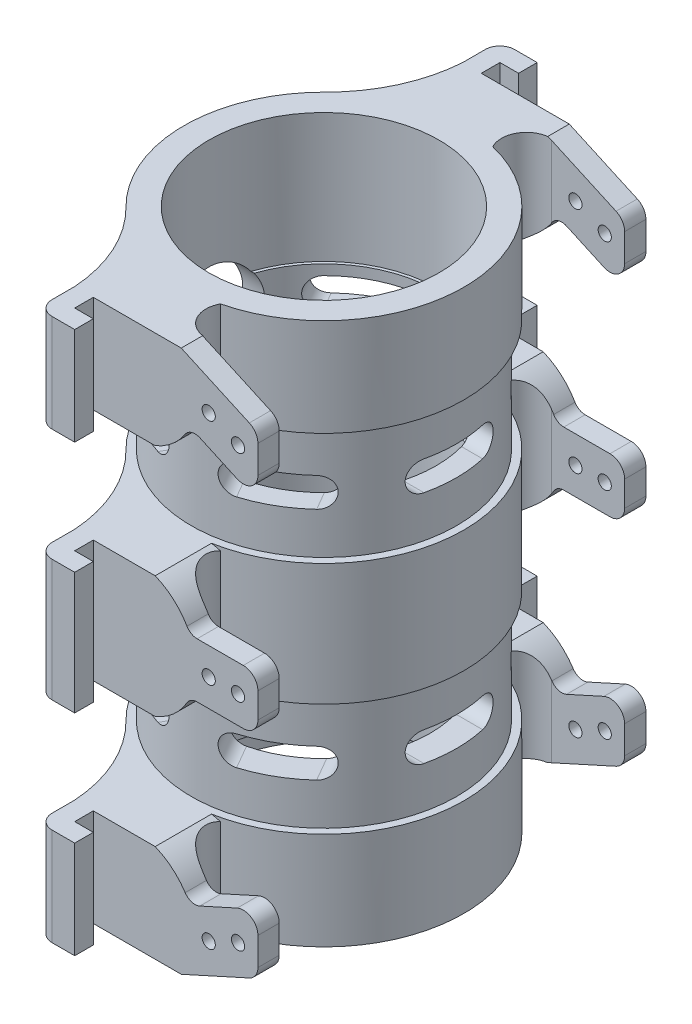
SolidWorks part; units mm, degrees
ref_plane "Front Plane" through (0, 0, 0) normal (0, 0, 1) x (1, 0, 0)
ref_plane "Top Plane" through (0, 0, 0) normal (0, 1, 0) x (1, 0, 0)
ref_plane "Right Plane" through (0, 0, 0) normal (1, 0, 0) x (0, 0, -1)
sketch "Sketch1" plane through (0, 0, 0) normal (0, 1, 0) x (1, 0, 0)
  line L0 (0, 38.25) -> (0, 45.25) construction
  circle A0 centre (0, 0) radius 38.25
  circle A1 centre (0, 0) radius 45.25
  dimension "D1" = 76.5
  dimension "D2" = 7
extrude "Boss-Extrude1" add sketch "Sketch1" along normal mid plane 185
sketch "Sketch2" plane through (0, -92.5, 0) normal (0, -1, 0) x (1, 0, 0)
  line L0 (0, 36.25) -> (0, 38.25) construction
  circle A0 centre (0, 0) radius 36.25
  circle A1 centre (0, 0) radius 38.25 construction
  circle A2 centre (0, 0) radius 38.25
  dimension "D1" = 2
extrude "Boss-Extrude2" add sketch "Sketch2" against normal blind 100 from offset 6.35 offset against normal yes
sketch "Sketch6" plane through (0, 92.5, 0) normal (0, 1, 0) x (1, 0, 0)
  line L0 (0, 38.25) -> (0, 39.25) construction
  circle A0 centre (0, 0) radius 39.25
  circle A1 centre (0, 0) radius 38.25 construction
  circle A2 centre (0, 0) radius 38.25
  dimension "D1" = 1
extrude "Cut-Extrude3" cut sketch "Sketch6" against normal blind 44
sketch "Sketch7" plane through (0, 0, 0) normal (1, 0, 0) x (0, 0, -1)
  line L0 (45.25, 92.5) -> (-45.25, 92.5) construction
  circle A0 centre (0, 40) radius 15
  dimension "D2" = 30
  dimension "D1" = 52.5
extrude "Cut-Extrude4" cut sketch "Sketch7" against normal through all
sketch "Sketch8" plane through (0, 0, 0) normal (0, 1, 0) x (1, 0, 0)
  line L1 (17.5, -66.175) -> (128.1882, -66.175) construction
  line L2 (-18.85, -66.175) -> (-18.85, -78.875)
  line L3 (-18.85, -78.875) -> (-6.15, -78.875)
  line L4 (45.25, 0) -> (-45.25, 0) construction
  line L5 (31.75, 0) -> (50, 0) construction
  line L6 (-6.15, -78.875) -> (-6.15, -72.525)
  line L7 (-12.5, -72.525) -> (17.5, -72.525) construction
  line L8 (-6.15, -72.525) -> (-12.5, -72.525)
  line L9 (-12.5, -72.525) -> (-12.5, -66.175)
  line L10 (-12.5, -66.175) -> (43.65, -66.175)
  line L11 (-12.5, 66.175) -> (43.65, 66.175)
  line L12 (-12.5, 72.525) -> (-12.5, 66.175)
  line L13 (-6.15, 72.525) -> (-12.5, 72.525)
  line L14 (-6.15, 78.875) -> (-6.15, 72.525)
  line L15 (-18.85, 78.875) -> (-6.15, 78.875)
  line L16 (-18.85, 66.175) -> (-18.85, 78.875)
  line L18 (43.65, -66.175) -> (43.65, -58.9107)
  line L19 (43.65, -58.9107) -> (18.65, -58.9107)
  line L20 (43.65, 58.9107) -> (18.65, 58.9107)
  line L21 (43.65, 66.175) -> (43.65, 58.9107)
  line L22 (-12.5, -72.525) -> (-18.85, -72.525) construction
  arc A0 (-32.8241, -31.1471) -> (-18.85, -66.175) centre (-69.7381, -66.175) cw
  circle A1 centre (0, 0) radius 45.25 construction
  arc A2 (-32.8241, -31.1471) -> (15.7007, -42.4388) centre (0, 0) ccw
  arc A3 (-32.8241, 31.1471) -> (15.7007, 42.4388) centre (0, 0) cw
  arc A4 (-32.8241, 31.1471) -> (-18.85, 66.175) centre (-69.7381, 66.175) ccw
  arc A9 (18.65, -58.9107) -> (15.7007, -42.4388) centre (18.65, -50.4107) cw
  arc A10 (18.65, 58.9107) -> (15.7007, 42.4388) centre (18.65, 50.4107) ccw
  point P6 (-18.6446, -78.6696)
  point P41 (0, 0)
  dimension "D1" = 8.5
  dimension "D2" = 62.5
  dimension "D3" = 25
extrude "Boss-Extrude3" add sketch "Sketch8" along normal up to surface and the other way up to surface up to face at (0, 92.5, 39.25) other way up to face at (0, -92.5, 45.25)
sketch "Sketch10" plane through (0, 0, 66.175) normal (0, 0, 1) x (1, 0, 0)
  line L0 (17.5, -92.5) -> (43.65, -92.5)
  line L1 (43.65, -92.5) -> (43.65, -80.6536)
  line L2 (-6.15, -59.2129) -> (-32.8241, -59.2129)
  line L3 (128.1882, -42.3564) -> (17.5, -92.5) construction
  line L4 (43.65, -80.6536) -> (17.5, -92.5)
  line L5 (43.65, 80.6536) -> (43.65, 92.5)
  line L6 (17.5, 92.5) -> (128.1882, 42.3564) construction
  line L7 (43.65, 92.5) -> (17.5, 92.5)
  line L8 (-12.5, 92.5) -> (43.65, 92.5) construction
  line L9 (17.5, 92.5) -> (43.65, 80.6536)
  line L10 (43.65, -60.1882) -> (43.65, -9.3209)
  line L11 (79.953, -43.7423) -> (23.8431, -69.161) construction
  line L12 (22.9086, -9.3209) -> (60.2886, -9.3209) construction
  line L21 (22.9086, -9.3209) -> (43.65, -9.3209)
  line L23 (43.65, -60.1882) -> (23.8431, -69.161)
  line L25 (-6.15, 92.5) -> (-6.15, -92.5) construction
  line L26 (-32.8241, 92.5) -> (-32.8241, -92.5) construction
  line L32 (-32.8241, -59.2129) -> (-32.8241, -20.7871)
  line L36 (-32.8241, -20.7871) -> (-6.15, -20.7871)
  line L40 (0, 0) -> (-32.8241, 0) construction
  line L45 (8.611, -59.2129) -> (-6.15, -59.2129)
  line L46 (8.611, -20.7871) -> (-6.15, -20.7871)
  line L47 (-32.8241, 59.2129) -> (-32.8241, 20.7871)
  line L48 (-6.15, 59.2129) -> (-32.8241, 59.2129)
  line L49 (8.611, 59.2129) -> (-6.15, 59.2129)
  line L50 (43.65, 60.1882) -> (23.8431, 69.161)
  line L51 (43.65, 60.1882) -> (43.65, 9.3209)
  line L52 (22.9086, 9.3209) -> (43.65, 9.3209)
  line L53 (8.611, 20.7871) -> (-6.15, 20.7871)
  line L54 (-32.8241, 20.7871) -> (-6.15, 20.7871)
  line L55 (43.65, 92.5) -> (43.65, -92.5) construction
  arc A6 (18.8427, -67.7035) -> (23.8431, -69.161) centre (22.1925, -65.5175) ccw construction
  arc A7 (18.8427, -67.7035) -> (8.611, -59.2129) centre (0, -80) ccw construction
  arc A10 (8.611, -20.7871) -> (19.4507, -11.3102) centre (0, 0) ccw construction
  arc A11 (22.9086, -9.3209) -> (19.4507, -11.3102) centre (22.9086, -13.3209) ccw construction
  arc A18 (18.8427, -67.7035) -> (23.8431, -69.161) centre (22.1925, -65.5175) ccw
  arc A19 (18.8427, -67.7035) -> (8.611, -59.2129) centre (0, -80) ccw
  arc A22 (8.611, -20.7871) -> (19.4507, -11.3102) centre (0, 0) ccw
  arc A23 (22.9086, -9.3209) -> (19.4507, -11.3102) centre (22.9086, -13.3209) ccw
  arc A24 (18.8427, 67.7035) -> (8.611, 59.2129) centre (0, 80) cw
  arc A25 (18.8427, 67.7035) -> (23.8431, 69.161) centre (22.1925, 65.5175) cw
  arc A26 (22.9086, 9.3209) -> (19.4507, 11.3102) centre (22.9086, 13.3209) cw
  arc A27 (8.611, 20.7871) -> (19.4507, 11.3102) centre (0, 0) cw
extrude "Cut-Extrude6" cut sketch "Sketch10" against normal up to surface and the other way through all up to face at (-45.1776, 54.7802, 2.5586)
sketch "Sketch11" plane through (0, 0, -78.875) normal (0, 0, -1) x (-1, 0, 0)
  line L3 (-43.65, 92.5) -> (-43.65, 80.6536)
  line L4 (-17.5, 92.5) -> (-43.65, 92.5)
  line L5 (-43.65, 80.6536) -> (-17.5, 92.5)
  line L6 (-43.65, 92.5) -> (-43.65, 80.6536)
  line L7 (-17.5, 92.5) -> (-43.65, 92.5)
  line L8 (-43.65, 80.6536) -> (-17.5, 92.5)
  line L9 (-43.65, -92.5) -> (-17.5, -92.5)
  line L10 (-43.65, -80.6536) -> (-43.65, -92.5)
  line L11 (-17.5, -92.5) -> (-43.65, -80.6536)
  line L12 (-43.65, -92.5) -> (-17.5, -92.5)
  line L13 (-43.65, -80.6536) -> (-43.65, -92.5)
  line L14 (-17.5, -92.5) -> (-43.65, -80.6536)
  line L20 (32.8241, 20.7871) -> (32.8241, 59.2129)
  line L21 (6.15, 20.7871) -> (32.8241, 20.7871)
  line L22 (-8.611, 20.7871) -> (6.15, 20.7871)
  line L23 (-43.65, 9.3209) -> (-22.9086, 9.3209)
  line L24 (-43.65, 60.1882) -> (-43.65, 9.3209)
  line L25 (-23.8431, 69.161) -> (-43.65, 60.1882)
  line L26 (6.15, 59.2129) -> (-8.611, 59.2129)
  line L27 (32.8241, 59.2129) -> (6.15, 59.2129)
  line L28 (32.8241, 20.7871) -> (32.8241, 59.2129)
  line L29 (6.15, 20.7871) -> (32.8241, 20.7871)
  line L30 (-8.611, 20.7871) -> (6.15, 20.7871)
  line L31 (-43.65, 9.3209) -> (-22.9086, 9.3209)
  line L32 (-43.65, 60.1882) -> (-43.65, 9.3209)
  line L33 (-23.8431, 69.161) -> (-43.65, 60.1882)
  line L34 (6.15, 59.2129) -> (-8.611, 59.2129)
  line L35 (32.8241, 59.2129) -> (6.15, 59.2129)
  line L36 (-22.9086, -9.3209) -> (-43.65, -9.3209)
  line L37 (-43.65, -9.3209) -> (-43.65, -60.1882)
  line L38 (-43.65, -60.1882) -> (-23.8431, -69.161)
  line L39 (-8.611, -59.2129) -> (6.15, -59.2129)
  line L40 (6.15, -59.2129) -> (32.8241, -59.2129)
  line L41 (32.8241, -59.2129) -> (32.8241, -20.7871)
  line L42 (32.8241, -20.7871) -> (6.15, -20.7871)
  line L43 (6.15, -20.7871) -> (-8.611, -20.7871)
  line L44 (-22.9086, -9.3209) -> (-43.65, -9.3209)
  line L45 (-43.65, -9.3209) -> (-43.65, -60.1882)
  line L46 (-43.65, -60.1882) -> (-23.8431, -69.161)
  line L47 (-8.611, -59.2129) -> (6.15, -59.2129)
  line L48 (6.15, -59.2129) -> (32.8241, -59.2129)
  line L49 (32.8241, -59.2129) -> (32.8241, -20.7871)
  line L50 (32.8241, -20.7871) -> (6.15, -20.7871)
  line L51 (6.15, -20.7871) -> (-8.611, -20.7871)
  arc A4 (-8.611, 20.7871) -> (-19.4507, 11.3102) centre (0, 0) ccw
  arc A5 (-22.9086, 9.3209) -> (-19.4507, 11.3102) centre (-22.9086, 13.3209) ccw
  arc A6 (-18.8427, 67.7035) -> (-23.8431, 69.161) centre (-22.1925, 65.5175) ccw
  arc A7 (-18.8427, 67.7035) -> (-8.611, 59.2129) centre (0, 80) ccw
  arc A8 (-8.611, 20.7871) -> (-19.4507, 11.3102) centre (0, 0) ccw
  arc A9 (-22.9086, 9.3209) -> (-19.4507, 11.3102) centre (-22.9086, 13.3209) ccw
  arc A10 (-18.8427, 67.7035) -> (-23.8431, 69.161) centre (-22.1925, 65.5175) ccw
  arc A11 (-18.8427, 67.7035) -> (-8.611, 59.2129) centre (0, 80) ccw
  arc A12 (-23.8431, -69.161) -> (-18.8427, -67.7035) centre (-22.1925, -65.5175) ccw
  arc A13 (-8.611, -59.2129) -> (-18.8427, -67.7035) centre (0, -80) ccw
  arc A14 (-19.4507, -11.3102) -> (-8.611, -20.7871) centre (0, 0) ccw
  arc A15 (-19.4507, -11.3102) -> (-22.9086, -9.3209) centre (-22.9086, -13.3209) ccw
  arc A16 (-23.8431, -69.161) -> (-18.8427, -67.7035) centre (-22.1925, -65.5175) ccw
  arc A17 (-8.611, -59.2129) -> (-18.8427, -67.7035) centre (0, -80) ccw
  arc A18 (-19.4507, -11.3102) -> (-8.611, -20.7871) centre (0, 0) ccw
  arc A19 (-19.4507, -11.3102) -> (-22.9086, -9.3209) centre (-22.9086, -13.3209) ccw
  dimension "D1" = 0
  dimension "D2" = 0
  dimension "D3" = 0
  dimension "D4" = 0
extrude "Cut-Extrude7" cut sketch "Sketch11" against normal up to surface (66.9486 mm away) up to face at (-3.9052, 0.3336, 17.6166)
fillet "Fillet4" radius 5 12 edges at (43.65, 80.6536, -62.5429) (43.65, 60.1882, -62.5429) (43.65, 9.3209, -62.5429) (43.65, -9.3209, -62.5429) (43.65, -60.1882, -62.5429) (43.65, -80.6536, -62.5429) (43.65, -80.6536, 62.5429) (43.65, -60.1882, 62.5429) (43.65, -9.3209, 62.5429) (43.65, 9.3209, 62.5429) (43.65, 60.1882, 62.5429) (43.65, 80.6536, 62.5429)
fillet "Fillet5" radius 5 6 edges at (-18.85, -75.8565, -78.875) (-18.85, 0, -78.875) (-18.85, 75.8565, -78.875) (-18.85, 0, 78.875) (-18.85, -75.8565, 78.875) (-18.85, 75.8565, 78.875)
sketch "Sketch14" plane through (0, 0, -66.175) normal (0, 0, -1) x (-1, 0, 0)
  line L0 (-36.867, 73.4937) -> (-26.867, 78.0239) construction
  line L1 (-17.5, 92.5) -> (-40.7132, 81.984) construction
  line L2 (-40.7132, 81.984) -> (-33.0207, 65.0034) construction
  line L3 (-36.5868, 63.3879) -> (-23.8431, 69.161) construction
  line L4 (0, 0) -> (-36.867, 0) construction
  line L5 (-26.867, 78.0239) -> (-26.867, 0) construction
  circle A2 centre (-36.867, 73.4937) radius 2.25
  circle A3 centre (-26.867, 78.0239) radius 2.25
  circle A4 centre (-36.867, 0) radius 2.25
  circle A5 centre (-26.867, 0) radius 2.25
  circle A6 centre (-36.867, -73.4937) radius 2.25
  circle A7 centre (-26.867, -78.0239) radius 2.25
  point P16 (-36.867, 73.4937)
  dimension "D1" = 4.5
  dimension "D2" = 10
extrude "Cut-Extrude8" cut sketch "Sketch14" against normal up to surface (7.2643 mm away) up to face at (30.7785, -73.3041, -58.9107)
sketch "Sketch15" plane through (0, 0, 66.175) normal (0, 0, 1) x (1, 0, 0)
  circle A1 centre (36.867, -73.4937) radius 2.25
  circle A2 centre (36.867, -73.4937) radius 2.25
  circle A3 centre (36.867, 0) radius 2.25
  circle A4 centre (36.867, 0) radius 2.25
  circle A5 centre (26.867, 78.0239) radius 2.25
  circle A6 centre (26.867, 78.0239) radius 2.25
  circle A7 centre (36.867, 73.4937) radius 2.25
  circle A8 centre (36.867, 73.4937) radius 2.25
  circle A9 centre (26.867, -78.0239) radius 2.25
  circle A10 centre (26.867, -78.0239) radius 2.25
  circle A11 centre (26.867, 0) radius 2.25
  circle A12 centre (26.867, 0) radius 2.25
  dimension "D1" = 0
  dimension "D2" = 0
  dimension "D3" = 0
  dimension "D4" = 0
  dimension "D5" = 0
  dimension "D6" = 0
extrude "Cut-Extrude9" cut sketch "Sketch15" against normal up to surface (7.2643 mm away) up to face at (30.7785, -73.3041, 58.9107)
sketch "Sketch16" plane through (0, 92.5, 0) normal (0, 1, 0) x (1, 0, 0)
  line L0 (-45.25, 0) -> (-47.75, 0) construction
  circle A0 centre (0, 0) radius 47.75
  circle A1 centre (0, 0) radius 45.25
  arc A2 (-32.8241, 31.1471) -> (-32.8241, -31.1471) centre (0, 0) ccw construction
  dimension "D1" = 2.5
extrude "Boss-Extrude4" add sketch "Sketch16" against normal up to surface (33.2871 mm away) up to face at (-10.3824, 59.2129, 65.577)
sketch "Sketch17" plane through (0, -92.5, 0) normal (0, -1, 0) x (1, 0, 0)
  circle A1 centre (0, 0) radius 45.25
  circle A2 centre (0, 0) radius 45.25
  circle A3 centre (0, 0) radius 47.75
  circle A4 centre (0, 0) radius 47.75
  dimension "D1" = 0
  dimension "D2" = 0
extrude "Boss-Extrude5" add sketch "Sketch17" against normal up to surface (33.2871 mm away) up to face at (-10.3824, -59.2129, 65.577)
sketch "Sketch18" plane through (0, -20.7871, 0) normal (0, -1, 0) x (1, 0, 0)
  circle A1 centre (0, 0) radius 47.75
  circle A2 centre (0, 0) radius 47.75
  circle A3 centre (0, 0) radius 45.25
  circle A4 centre (0, 0) radius 45.25
  dimension "D1" = 0
  dimension "D2" = 0
extrude "Boss-Extrude6" add sketch "Sketch18" against normal up to surface (41.5741 mm away) up to face at (-10.3824, 20.7871, 65.577)
sketch "Sketch20" plane through (0, 0, 0) normal (1, 0, 0) x (0, 0, -1)
  line L0 (-45.25, -20.7871) -> (45.25, -20.7871) construction
  line L1 (46.9672, -59.2129) -> (-46.9672, -59.2129) construction
  line L2 (-45.25, 59.2129) -> (45.25, 59.2129) construction
  line L3 (46.9672, 20.7871) -> (-46.9672, 20.7871) construction
  line L4 (-45.25, -20.7871) -> (45.25, -20.7871) construction
  line L5 (46.9672, -59.2129) -> (-46.9672, -59.2129) construction
  line L6 (-45.25, 59.2129) -> (45.25, 59.2129) construction
  line L7 (46.9672, 20.7871) -> (-46.9672, 20.7871) construction
  line L8 (0, -20.7871) -> (0, -59.2129) construction
  line L9 (0, 59.2129) -> (0, 20.7871) construction
  line L10 (-10, 40) -> (10, 40) construction
  line L11 (-10, 45) -> (10, 45)
  line L12 (-10, 35) -> (10, 35)
  line L13 (0, 0) -> (46.4328, 0) construction
  line L14 (46.4328, 19.5496) -> (46.4328, -19.5496) construction
  line L15 (-10, -40) -> (10, -40) construction
  line L16 (-10, -45) -> (10, -45)
  line L17 (-10, -35) -> (10, -35)
  arc A2 (-10, 45) -> (-10, 35) centre (-10, 40) ccw
  arc A3 (10, 35) -> (10, 45) centre (10, 40) ccw
  arc A4 (-10, -45) -> (-10, -35) centre (-10, -40) cw
  arc A5 (10, -35) -> (10, -45) centre (10, -40) cw
  point P2 (0, 40)
  point P14 (0, -20.7871)
  point P30 (0, -40)
  dimension "D1" = 20
  dimension "D2" = 5
extrude "Cut-Extrude10" cut sketch "Sketch20" along normal through all
pattern_circular "CirPattern1" count 6 over 360 about axis through (0, 92.5, 0) along (0, -1, 0) of "Cut-Extrude10" reverse direction yes
ref_plane "Plane1" through (-26.1107, -92.5, 39.9787) normal (0, -1, 0) x (-1, 0, 0)
sketch "Sketch23" plane through (0, -92.5, 0) normal (0, -1, 0) x (1, 0, 0)
  line L0 (0, 0) -> (-47.75, 0) construction
  arc A0 (-18.85, 66.175) -> (-33.5786, 33.9491) centre (-68.7395, 69.4978) cw
  arc A1 (-26.1107, 39.9787) -> (-26.1107, -39.9787) centre (0, 0) ccw construction
  arc A2 (-33.5786, 33.9491) -> (-26.1107, 39.9787) centre (0, 0) cw
  arc A3 (-18.85, 66.175) -> (-26.1107, 39.9787) centre (-69.7381, 66.175) cw
  arc A4 (-18.85, -66.175) -> (-26.1107, -39.9787) centre (-69.7381, -66.175) ccw
  arc A5 (-33.5786, -33.9491) -> (-26.1107, -39.9787) centre (0, 0) ccw
  arc A6 (-18.85, -66.175) -> (-33.5786, -33.9491) centre (-68.7395, -69.4978) ccw
  arc A7 (-26.1107, 39.9787) -> (-18.85, 66.175) centre (-69.7381, 66.175) ccw construction
  point P20 (-33.935, 33.5928)
  dimension "D1" = 50
extrude "Boss-Extrude7" add sketch "Sketch23" against normal up to surface (33.2871 mm away) up to face at (-8.8243, -59.2129, 0)
sketch "Sketch24" plane through (0, 92.5, 0) normal (0, 1, 0) x (1, 0, 0)
  arc A3 (-26.1107, 39.9787) -> (-18.85, 66.175) centre (-69.7381, 66.175) ccw
  arc A4 (-26.1107, 39.9787) -> (-33.5786, 33.9491) centre (0, 0) ccw
  arc A5 (-33.5786, 33.9491) -> (-18.85, 66.175) centre (-68.7395, 69.4978) ccw
  arc A6 (-26.1107, 39.9787) -> (-18.85, 66.175) centre (-69.7381, 66.175) ccw
  arc A7 (-26.1107, 39.9787) -> (-33.5786, 33.9491) centre (0, 0) ccw
  arc A8 (-33.5786, 33.9491) -> (-18.85, 66.175) centre (-68.7395, 69.4978) ccw
  arc A9 (-18.85, -66.175) -> (-33.5786, -33.9491) centre (-68.7395, -69.4978) ccw
  arc A10 (-33.5786, -33.9491) -> (-26.1107, -39.9787) centre (0, 0) ccw
  arc A11 (-18.85, -66.175) -> (-26.1107, -39.9787) centre (-69.7381, -66.175) ccw
  arc A12 (-18.85, -66.175) -> (-33.5786, -33.9491) centre (-68.7395, -69.4978) ccw
  arc A13 (-33.5786, -33.9491) -> (-26.1107, -39.9787) centre (0, 0) ccw
  arc A14 (-18.85, -66.175) -> (-26.1107, -39.9787) centre (-69.7381, -66.175) ccw
  dimension "D1" = 0
  dimension "D2" = 0
extrude "Boss-Extrude8" add sketch "Sketch24" against normal up to surface (33.2871 mm away) up to face at (-45.25, 59.2129, 0)
sketch "Sketch25" plane through (0, 20.7871, 0) normal (0, 1, 0) x (1, 0, 0)
  arc A3 (-18.85, -66.175) -> (-33.5786, -33.9491) centre (-68.7395, -69.4978) ccw
  arc A4 (-33.5786, -33.9491) -> (-26.1107, -39.9787) centre (0, 0) ccw
  arc A5 (-18.85, -66.175) -> (-26.1107, -39.9787) centre (-69.7381, -66.175) ccw
  arc A6 (-18.85, -66.175) -> (-33.5786, -33.9491) centre (-68.7395, -69.4978) ccw
  arc A7 (-33.5786, -33.9491) -> (-26.1107, -39.9787) centre (0, 0) ccw
  arc A8 (-18.85, -66.175) -> (-26.1107, -39.9787) centre (-69.7381, -66.175) ccw
  arc A9 (-26.1107, 39.9787) -> (-18.85, 66.175) centre (-69.7381, 66.175) ccw
  arc A10 (-33.5786, 33.9491) -> (-18.85, 66.175) centre (-68.7395, 69.4978) ccw
  arc A11 (-26.1107, 39.9787) -> (-33.5786, 33.9491) centre (0, 0) ccw
  arc A12 (-26.1107, 39.9787) -> (-18.85, 66.175) centre (-69.7381, 66.175) ccw
  arc A13 (-33.5786, 33.9491) -> (-18.85, 66.175) centre (-68.7395, 69.4978) ccw
  arc A14 (-26.1107, 39.9787) -> (-33.5786, 33.9491) centre (0, 0) ccw
  dimension "D1" = 0
  dimension "D2" = 0
extrude "Boss-Extrude9" add sketch "Sketch25" against normal up to surface (41.5741 mm away) up to face at (-45.25, -20.7871, 0)
